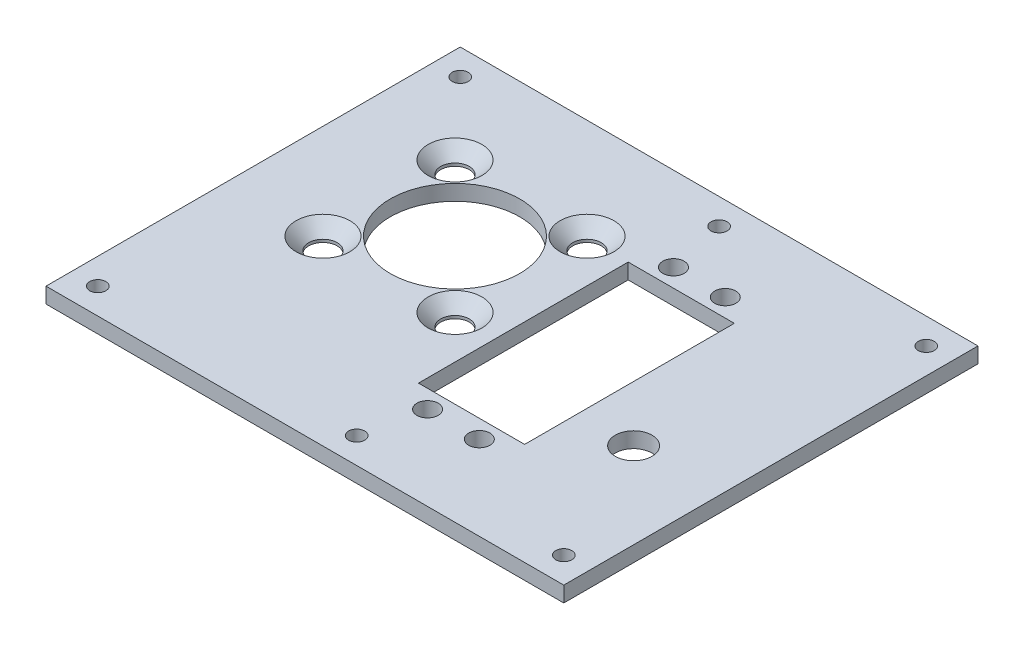
SolidWorks part; units mm, degrees
ref_plane "Płaszczyzna przednia" through (0, 0, 0) normal (0, 0, 1) x (1, 0, 0)
ref_plane "Płaszczyzna górna" through (0, 0, 0) normal (0, 1, 0) x (1, 0, 0)
ref_plane "Płaszczyzna prawa" through (0, 0, 0) normal (1, 0, 0) x (0, 0, -1)
sketch "Szkic1" plane through (0, 0, 0) normal (0, 1, 0) x (1, 0, 0)
  line L6 (-20.2688, 11.7569) -> (5.2312, -13.7431) construction
  line L11 (-38.6633, 31.161) -> (61.3367, 31.161)
  line L12 (-38.6633, 31.161) -> (-38.6633, -48.839)
  line L13 (-38.6633, -48.839) -> (61.3367, -48.839)
  line L14 (61.3367, 31.161) -> (61.3367, -48.839)
  line L15 (-20.2688, -13.7431) -> (5.2312, 11.7569) construction
  line L17 (13.5251, 11.411) -> (34.0251, 11.411)
  line L18 (13.5251, 11.411) -> (13.5251, -29.089)
  line L23 (13.5251, -29.089) -> (34.0251, -29.089)
  line L24 (34.0251, 11.411) -> (34.0251, -29.089)
  circle A0 centre (-7.5188, -0.9931) radius 12.5
  circle A2 centre (-20.2688, 11.7569) radius 2.55
  circle A3 centre (5.2312, 11.7569) radius 2.55
  circle A4 centre (5.2312, -13.7431) radius 2.55
  circle A5 centre (-20.2688, -13.7431) radius 2.55
  circle A6 centre (18.7751, 14.911) radius 2.05
  circle A7 centre (28.7751, 14.911) radius 2.05
  circle A8 centre (18.7751, -32.589) radius 2.05
  circle A9 centre (28.7751, -32.589) radius 2.05
  circle A10 centre (23.7751, -18.789) radius 0.5
  circle A11 centre (-7.5188, -0.9931) radius 0.5
  circle A12 centre (44.7751, -18.789) radius 3.55
  circle A13 centre (44.7751, -18.789) radius 0.5
  circle A14 centre (-33.6633, 26.161) radius 1.55
  circle A15 centre (56.3367, 26.161) radius 1.55
  circle A16 centre (56.3367, -43.839) radius 1.55
  circle A17 centre (-33.6633, -43.839) radius 1.55
  circle A18 centre (16.3367, 26.161) radius 1.55
  circle A19 centre (16.3367, -43.839) radius 1.55
  point P18 (23.7751, -29.089)
  point P22 (23.7751, 11.411)
  point P27 (11.3367, -8.839)
  dimension "D3" = 10.3
  dimension "D5" = 3.5
  dimension "D13" = 36
  dimension "D18" = 19.75
  dimension "D20" = 5.1
  dimension "D22" = 25
  dimension "D23" = 7.1
  dimension "D24" = 4.1
  dimension "D25" = 47.5
  dimension "D1" = 100
  dimension "D2" = 80
  dimension "D4" = 10.25
  dimension "D6" = 3.5
  dimension "D7" = 5
  dimension "D8" = 5
  dimension "D9" = 3.5
  dimension "D10" = 3.5
  dimension "D11" = 5
  dimension "D12" = 5
  dimension "D14" = 21
  dimension "D15" = 40.5
  dimension "D16" = 20.5
  dimension "D17" = 10.3
  dimension "D19" = 19.75
  dimension "D21" = 25.5
extrude "Dodanie-wyciągnięcie1" add sketch "Szkic1" along normal blind 3 contours L14 L11 L12 L13 A12 A9 A8 A7 A6 A5 A4 A3 A2 A0 L17 L24 L23 L18 region at (11.0911, 0, 9.4735)
sketch "Sketch1" plane through (0, 0, 0) normal (0, 1, 0) x (1, 0, 0)
  point P0 (-20.2688, -13.7431)
  point P3 (5.2312, -13.7431)
  point P6 (5.2312, 11.7569)
  point P9 (-20.2688, 11.7569)
sketch "Sketch3" plane through (0, 3, 0) normal (0, 1, 0) x (1, 0, 0)
  point P0 (-20.2688, -13.7431)
  point P3 (5.2312, -13.7431)
  point P6 (5.2312, 11.7569)
  point P9 (-20.2688, 11.7569)
hole_wizard "CSK for M5 Countersunk Flat Head Screw2" positions "Sketch3" profile "Sketch4" countersink size "M5" standard "ISO" end condition through all
sketch "Sketch4" plane through (-20.2688, 3, 13.7431) normal (1, 0, 0) x (0, 0, 1)
  line L0 (0, 0) -> (0, 3)
  line L1 (0, 3) -> (2.75, 3)
  line L2 (2.75, 3) -> (2.75, 2.45)
  line L3 (2.75, 2.45) -> (5.2, 0)
  line L5 (5.2, 0) -> (0, 0)
  line L6 (-2.75, 2.45) -> (-5.2, 0) construction
  line L11 (0, -6.35) -> (0, 107.95) construction
  dimension "Thru Hole Dia." = 5.5
  dimension "Thru Hole Depth" = 3
  dimension "Near C'Sink Dia." = 10.4
  dimension "Near C'Sink Angle" = 90
